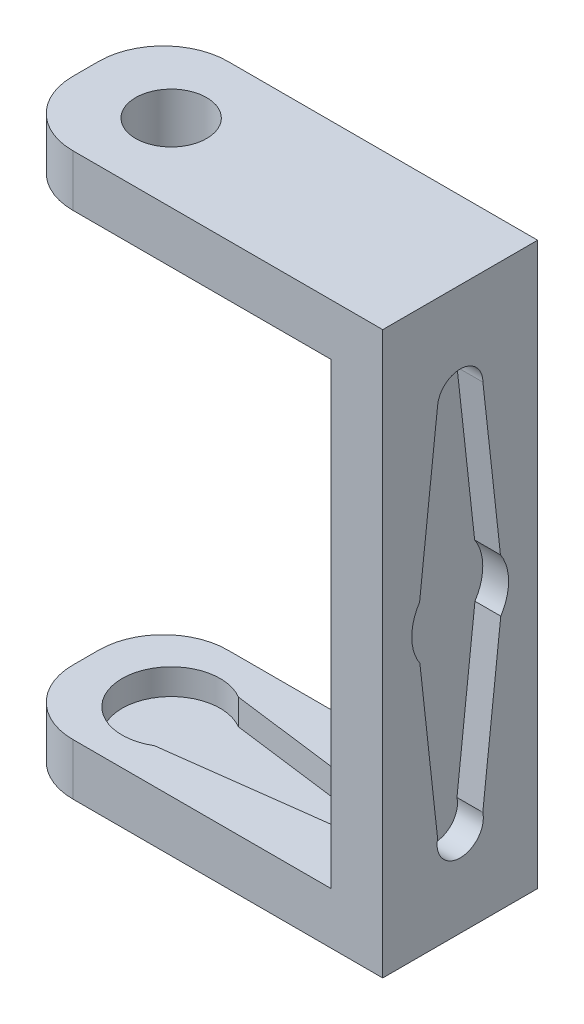
SolidWorks part; units mm, degrees
ref_plane "Front Plane" through (0, 0, 0) normal (0, 0, 1) x (1, 0, 0)
ref_plane "Top Plane" through (0, 0, 0) normal (0, 1, 0) x (1, 0, 0)
ref_plane "Right Plane" through (0, 0, 0) normal (1, 0, 0) x (0, 0, -1)
sketch "Sketch1" plane through (0, 0, 0) normal (0, 1, 0) x (1, 0, 0)
  line L0 (0, 0) -> (15.85, 0) construction
  line L4 (14.2423, 1.667) -> (1.9516, 3.2606)
  line L5 (14.2423, -1.667) -> (1.9516, -3.2606)
  arc A12 (1.9516, 3.2606) -> (1.9516, -3.2606) centre (0, 0) ccw
  arc A13 (14.2423, -1.667) -> (14.2423, 1.667) centre (14.2423, 0) ccw
sketch3d "3DSketch2" plane through (0, 0, 0) normal (0, 0, 1) x (1, 0, 0)
  dimension "D1" = 1.5
sketch "Sketch3" plane through (0, 0, 0) normal (0, 1, 0) x (1, 0, 0)
  line L1 (-6.6092, 6) -> (18.3908, 6)
  line L2 (-6.6092, 6) -> (-6.6092, -6)
  line L3 (-6.6092, -6) -> (18.3908, -6)
  line L4 (18.3908, 6) -> (18.3908, -6)
  line L5 (0, 0) -> (15.85, 0) construction
  dimension "D1" = 25
  dimension "D2" = 12
  dimension "D3" = 6
  dimension "D4" = 18.3908
extrude "Boss-Extrude1" add sketch "Sketch3" against normal blind 4
extrude "single horn" cut sketch "Sketch1" against normal blind 2
sketch "Sketch4" plane through (0, -4, 0) normal (0, -1, 0) x (1, 0, 0)
  line L1 (18.3908, 6) -> (22.3908, 6)
  line L2 (18.3908, 6) -> (18.3908, -6)
  line L3 (18.3908, -6) -> (22.3908, -6)
  line L4 (22.3908, 6) -> (22.3908, -6)
extrude "Boss-Extrude2" add sketch "Sketch4" against normal blind 43.5
sketch "Sketch5" plane through (0, 39.5, 0) normal (0, 1, 0) x (1, 0, 0)
  line L1 (18.3908, 6) -> (-6.6092, 6)
  line L2 (18.3908, 6) -> (18.3908, -6)
  line L3 (18.3908, -6) -> (-6.6092, -6)
  line L4 (-6.6092, 6) -> (-6.6092, -6)
extrude "Boss-Extrude4" add sketch "Sketch5" against normal blind 4 contours L3 L4 L1 L2
sketch "Sketch6" plane through (0, 39.5, 0) normal (0, 1, 0) x (1, 0, 0)
  circle A0 centre (0, 0) radius 2.75
  dimension "D1" = 5.5
extrude "Cut-Extrude3" cut sketch "Sketch6" against normal blind 4
fillet "Fillet1" radius 5 4 edges at (-6.6092, -2, -6) (-6.6092, 37.5, 6) (-6.6092, 37.5, -6) (-6.6092, -2, 6)
sketch "Sketch11" plane through (22.3908, 0, 0) normal (1, 0, 0) x (0, 0, -1)
  line L0 (0, 17.75) -> (0, 33.6) construction
  line L1 (-1.7516, 32.2635) -> (-3.1445, 19.7932)
  line L2 (3.1206, 19.8296) -> (1.7592, 32.1)
  line L3 (6, -4) -> (-6, -4) construction
  line L4 (0.0013, 17.2004) -> (0.0013, 1.3504) construction
  line L5 (1.7516, 3.2365) -> (3.1445, 15.7068)
  line L6 (-3.1206, 15.6704) -> (-1.7496, 3.2336)
  arc A0 (-3.1445, 19.7932) -> (-3.1206, 15.6704) centre (0, 17.75) ccw
  arc A9 (1.7592, 32.1) -> (-1.7516, 32.2635) centre (0, 32.1) ccw
  arc A16 (-1.7496, 3.2336) -> (1.7516, 3.2365) centre (0.0013, 2.8504) ccw
  arc A17 (3.1445, 15.7068) -> (3.1206, 19.8296) centre (0, 17.75) ccw
  dimension "D1" = 21.75
extrude "double horn" cut sketch "Sketch11" against normal blind 2
